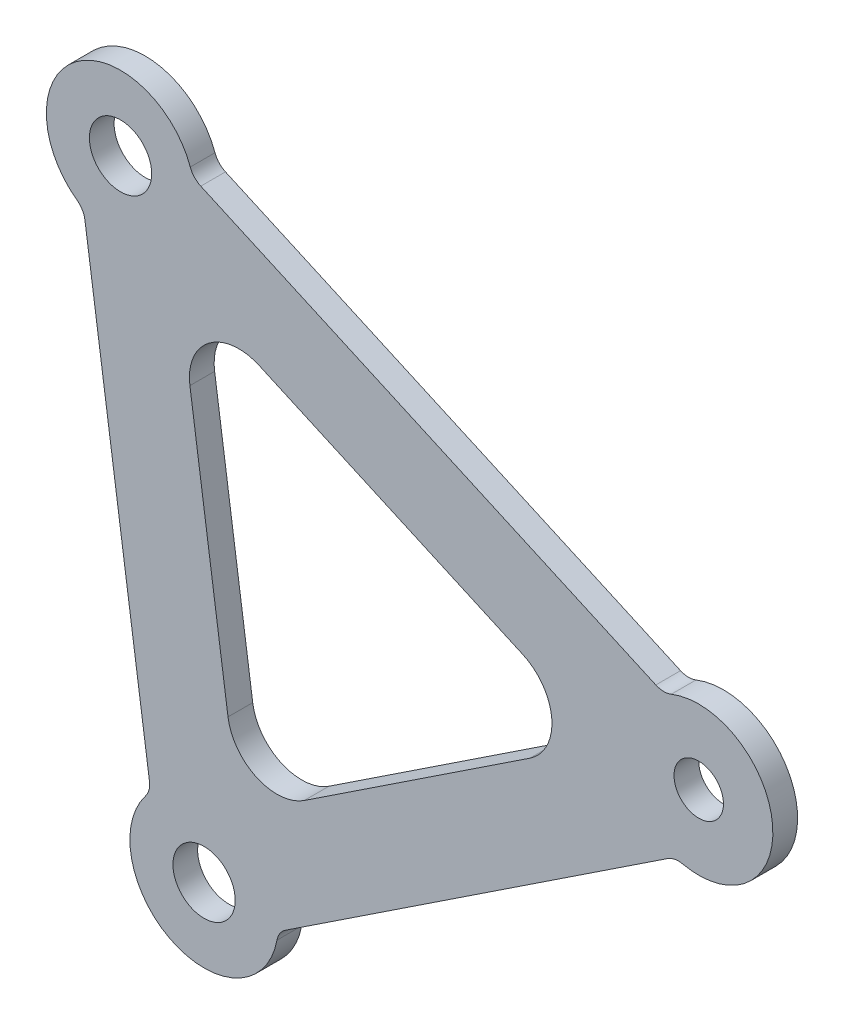
SolidWorks part; units mm, degrees
other "Static 1"
material "6061-T6 (SS)"
ref_plane "Front Plane" through (0, 0, 0) normal (0, 0, 1) x (1, 0, 0)
ref_plane "Top Plane" through (0, 0, 0) normal (0, 1, 0) x (1, 0, 0)
ref_plane "Right Plane" through (0, 0, 0) normal (1, 0, 0) x (0, 0, -1)
sketch "Sketch1" plane through (0, 0, 1577.6299) normal (0, 0, 1) x (1, 0, 0)
  line L0 (290.3087, 659.2798) -> (226.7802, 617.2016) construction
  line L1 (216.0509, 692.6424) -> (226.7802, 617.2016) construction
  line L2 (290.3087, 659.2798) -> (226.7802, 617.2016) construction
  line L3 (216.0509, 692.6424) -> (226.7802, 617.2016) construction
  line L4 (216.0509, 692.6424) -> (290.3087, 659.2798) construction
  line L5 (200.2322, 713.6724) -> (217.0368, 595.5148)
  line L6 (217.0368, 595.5148) -> (316.5369, 661.4188)
  line L7 (316.5369, 661.4188) -> (200.2322, 713.6724)
  line L9 (253.1798, 675.9611) -> (258.3845, 687.5456) construction
  line L10 (208.8421, 653.1338) -> (221.4156, 654.922) construction
  line L11 (258.5445, 638.2407) -> (265.5575, 627.6526) construction
  circle A0 centre (216.0509, 692.6424) radius 4 construction
  circle A1 centre (290.3087, 659.2798) radius 3.175 construction
  circle A2 centre (216.0509, 692.6424) radius 4
  circle A3 centre (290.3087, 659.2798) radius 3.175
  circle A4 centre (226.7802, 617.2016) radius 4
  point P22 (253.1798, 675.9611)
  point P24 (221.4156, 654.922)
  point P26 (258.5445, 638.2407)
  dimension "D1" = 12.7
extrude "Boss-Extrude1" add sketch "Sketch1" along normal blind 3.175 contours L5 L6 L7
fillet "Fillet1" [suppressed] radius 10.16
extrude "Holes" cut sketch "Sketch1<4>" along normal blind 3.175 contours A3 | A2 | A4
sketch "Sketch1<4>" plane through (0, 0, 1577.6299) normal (0, 0, 1) x (1, 0, 0) same geometry as "Sketch1"
sketch "Sketch5" plane through (0, 0, 1577.6299) normal (0, 0, -1) x (-1, 0, 0)
  line L0 (-211.3158, 684.3778) -> (-219.9286, 623.8183)
  line L1 (-236.2773, 616.4732) -> (-287.2743, 650.2511)
  line L2 (-225.3045, 694.9001) -> (-285.8514, 667.6975)
  line L3 (-216.0509, 692.6424) -> (-290.3087, 659.2798) construction
  line L4 (-216.0509, 692.6424) -> (-226.7802, 617.2016) construction
  line L5 (-290.3087, 659.2798) -> (-226.7802, 617.2016) construction
  line L6 (-215.2837, 656.4782) -> (-221.0771, 657.3021) construction
  line L7 (-251.1479, 676.874) -> (-253.546, 682.2117) construction
  line L8 (-260.0207, 639.2185) -> (-263.2521, 634.3399) construction
  arc A0 (-225.3045, 694.9001) -> (-211.3158, 684.3778) centre (-216.0509, 692.6424) cw
  arc A1 (-219.9286, 623.8183) -> (-236.2773, 616.4732) centre (-226.7802, 617.2016) cw
  arc A2 (-287.2743, 650.2511) -> (-285.8514, 667.6975) centre (-290.3087, 659.2798) cw
extrude "OutsideExtrude" cut sketch "Sketch5" against normal blind 3.81 flip side to cut
sketch "Sketch6" plane through (0, 0, 1577.6299) normal (0, 0, -1) x (-1, 0, 0)
  line L3 (-223.3396, 682.9527) -> (-231.2697, 627.194)
  line L4 (-231.2697, 627.194) -> (-278.2238, 658.2942)
  line L5 (-278.2238, 658.2942) -> (-223.3396, 682.9527)
  line L6 (-219.9727, 665.067) -> (-225.7661, 665.8909) construction
  line L7 (-216.0509, 692.6424) -> (-226.7802, 617.2016) construction
  line L8 (-241.3468, 674.8623) -> (-243.7449, 680.2) construction
  line L10 (-260.651, 646.6548) -> (-263.8823, 641.7762) construction
  line L11 (-290.3087, 659.2798) -> (-226.7802, 617.2016) construction
  line L12 (-214.7903, 659.9473) -> (-220.5837, 660.7713) construction
  line L13 (-211.3158, 684.3778) -> (-219.9286, 623.8183) construction
  line L14 (-216.0509, 692.6424) -> (-290.3087, 659.2798) construction
extrude "InnerTriangle" cut sketch "Sketch6" against normal blind 3.81 contours L3 L4 L5
fillet "Fillet2" radius 6.35 3 edges at (278.2238, 658.2942, 1579.2174) (231.2697, 627.194, 1579.2174) (223.3396, 682.9527, 1579.2174)
sketch "Force Reference" plane through (0, 0, 1580.8049) normal (0, 0, 1) x (1, 0, 0)
  line L0 (290.3087, 659.2798) -> (303.1908, 639.8308) construction
  line L1 (236.2773, 616.4732) -> (287.2743, 650.2511) construction
  line L2 (216.0509, 692.6424) -> (189.3852, 688.85) construction
  line L3 (211.3158, 684.3778) -> (219.9286, 623.8183) construction
fillet "Fillet3" radius 2.54 6 edges at (285.8514, 667.6975, 1579.2174) (287.2743, 650.2511, 1579.2174) (236.2773, 616.4732, 1579.2174) (219.9286, 623.8183, 1579.2174) (211.3158, 684.3778, 1579.2174) (225.3045, 694.9001, 1579.2174)
